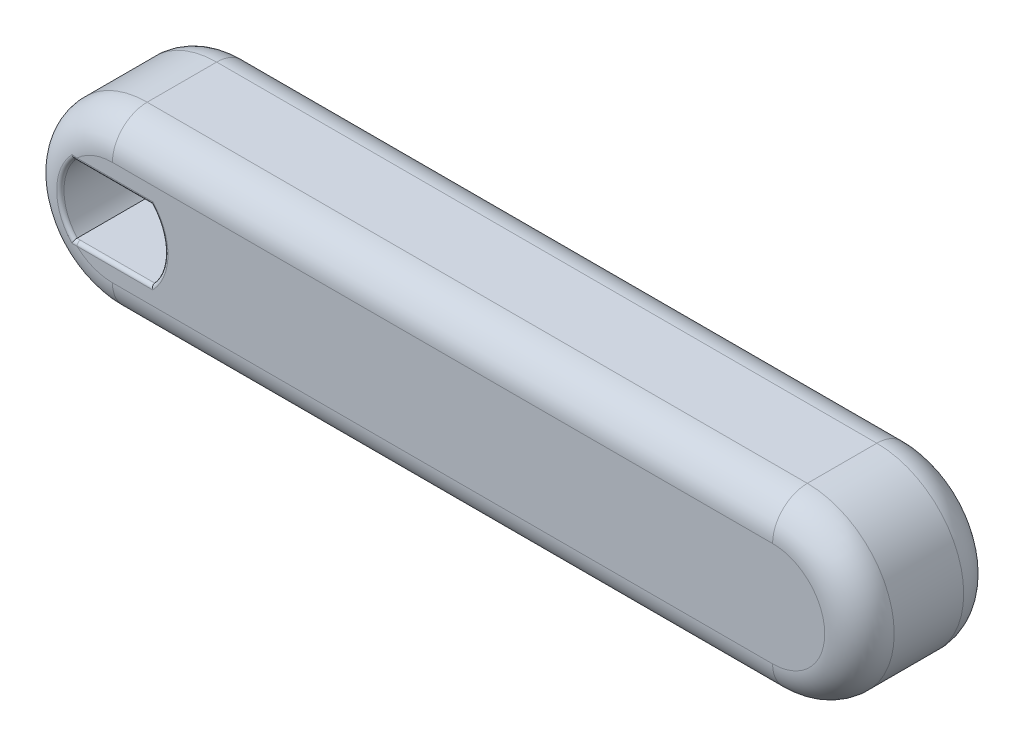
SolidWorks part; units mm, degrees
ref_plane "Front Plane" through (0, 0, 0) normal (0, 0, 1) x (1, 0, 0)
ref_plane "Top Plane" through (0, 0, 0) normal (0, 1, 0) x (1, 0, 0)
ref_plane "Right Plane" through (0, 0, 0) normal (1, 0, 0) x (0, 0, -1)
sketch "Sketch1" plane through (0, 0, 0) normal (0, 0, 1) x (1, 0, 0)
  line L0 (-12.5, 12.5) -> (107.5, -12.5) construction
  line L1 (-12.5, 12.5) -> (107.5, 12.5)
  line L2 (-12.5, 12.5) -> (-12.5, -12.5)
  line L3 (-12.5, -12.5) -> (107.5, -12.5)
  line L4 (107.5, 12.5) -> (107.5, -12.5)
  line L5 (0, 0) -> (47.5, 0) construction
  circle A0 centre (0, 0) radius 12.5
  circle A1 centre (95, 0) radius 12.5
  dimension "D1" = 120
  dimension "D2" = 25
extrude "Boss-Extrude1" add sketch "Sketch1" along normal blind 20 contours A0 L3 L4 L1 | A0 | A1 region at (47.5, 0, 0) region at (0, 0, 0) region at (95, 0, 0)
sketch "Sketch2" plane through (0, 0, 20) normal (0, 0, 1) x (1, 0, 0)
  line L0 (-5.5902, 5) -> (5.5902, 5)
  line L1 (0, 5) -> (0, -5) construction
  line L2 (5.5902, -5) -> (-5.5902, -5)
  circle A0 centre (0, 0) radius 7.5
  dimension "D1" = 15
  dimension "D2" = 10
extrude "Cut-Extrude1" cut sketch "Sketch2" against normal through all contours L0 L1 L2 A0 | L1 L0 A0 L2 region at (-3.4723, 0, 20) region at (3.4723, 0, 20)
fillet "Fillet3" radius 5 8 edges at (-12.5, 0, 20) (47.5, -12.5, 20) (107.5, 0, 20) (-12.5, 0, 0) (47.5, -12.5, 0) (107.5, 0, 0) (47.5, 12.5, 20) (47.5, 12.5, 0)
sketch "Sketch3" plane through (0, 0, 20) normal (0, 0, 1) x (1, 0, 0)
  circle A0 centre (0, 0) radius 7.5
  arc A1 (5.5902, -5) -> (5.5902, 5) centre (0, 0) ccw construction
  circle A2 centre (0, 0) radius 2.25
  dimension "D1" = 4.5
extrude "Boss-Extrude2" add sketch "Sketch3" against normal blind 5
fillet "Fillet4" radius 0.5 6 edges at (-7.5, 0, 0) (0, 5, 0) (0, -5, 0) (7.5, 0, 0) (2.25, 0, 15) (2.25, 0, 20)
mirror "Mirror1" about plane through (0, 0, 0) normal (0, 0, 1) of bodies 103 104
delete or keep bodies "Body-Delete/Keep 1" type delete bodies bodies 103
sketch "Sketch4" plane through (0, 0, -20) normal (0, 0, -1) x (-1, 0, 0)
  line L0 (-102.5, 0) -> (-2.75, 0) construction
  line L1 (-102.5, 0) -> (-102.5, -7.5) construction
  line L3 (-2.75, 0) -> (-2.75, -10) construction
  line L4 (-102.5, -3.25) -> (-2.75, -3.25) construction
  text T0 "ECO-MAUÁ URBANO" font "Arial Rounded MT Bold" height 6.5
  dimension "D1" = 3.25
extrude "Cut-Extrude2" cut sketch "Sketch4" against normal blind 0.2
